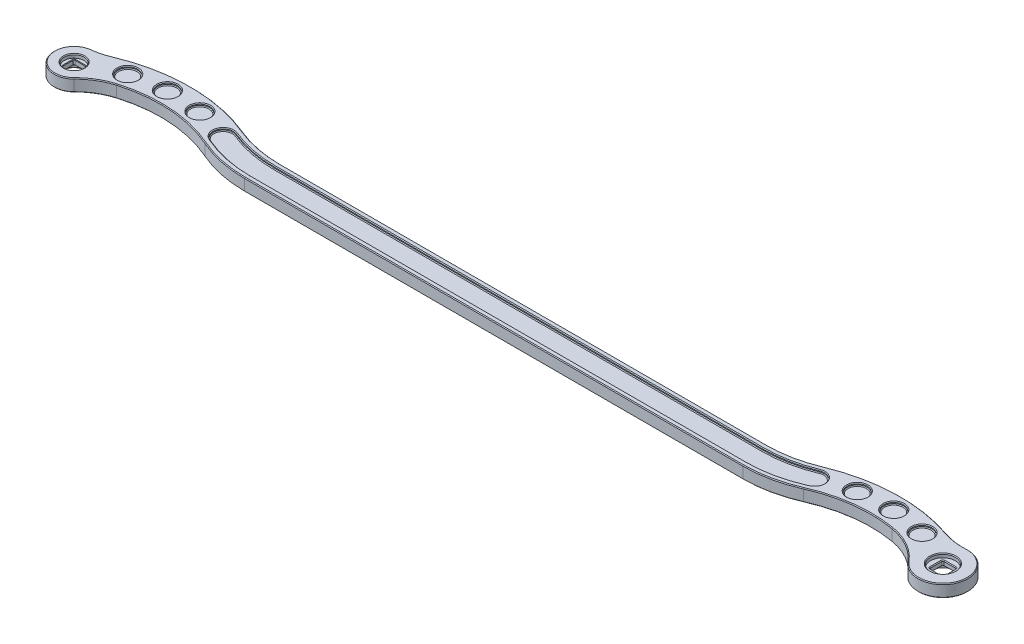
SolidWorks part; units mm, degrees
material "보통 탄소강"
ref_plane "정면" through (0, 0, 0) normal (0, 0, 1) x (1, 0, 0)
ref_plane "윗면" through (0, 0, 0) normal (0, 1, 0) x (1, 0, 0)
ref_plane "우측면" through (0, 0, 0) normal (1, 0, 0) x (0, 0, -1)
sketch "스케치1" plane through (0, 0, 0) normal (0, 1, 0) x (1, 0, 0)
  line L0 (0, 0) -> (350, 0) construction
  line L1 (77.0777, 6) -> (272.9223, 6)
  line L2 (74.6146, -6) -> (275.3854, -6)
  line L3 (335, 6.5992) -> (318, -52.3889) construction
  line L4 (75.0349, -4) -> (274.9651, -4)
  line L5 (0, 0) -> (32, 0) construction
  line L6 (32, 3) -> (32, 15) construction
  line L7 (32, 3) -> (32, 9) construction
  line L8 (175, 6) -> (175, -6) construction
  line L9 (273.3234, 4) -> (76.6766, 4)
  line L10 (307.4208, 8.0816) -> (318, -52.3889) construction
  line L11 (321.2949, 8.9115) -> (318, -52.3889) construction
  line L12 (294.089, 4.1521) -> (318, -52.3889) construction
  line L14 (347.25, -2.75) -> (352.75, -2.75)
  line L15 (347.25, -2.75) -> (347.25, 2.75)
  line L16 (347.25, 2.75) -> (352.75, 2.75)
  line L17 (352.75, -2.75) -> (352.75, 2.75)
  line L18 (347.25, -2.75) -> (352.75, 2.75) construction
  line L19 (347.25, 2.75) -> (352.75, -2.75) construction
  line L20 (2.5, -2.5) -> (-2.5, -2.5)
  line L21 (2.5, -2.5) -> (2.5, 2.5)
  line L22 (2.5, 2.5) -> (-2.5, 2.5)
  line L23 (-2.5, -2.5) -> (-2.5, 2.5)
  line L24 (2.5, -2.5) -> (-2.5, 2.5) construction
  line L25 (2.5, 2.5) -> (-2.5, -2.5) construction
  circle A2 centre (0, 0) radius 8
  circle A3 centre (350, 0) radius 10
  circle A6 centre (350, 0) radius 5
  circle A9 centre (32, 0) radius 3
  arc A11 (72.1368, -5.9386) -> (-6.5409, -4.6061) centre (32, -52.3889) ccw
  arc A12 (54.3968, -1.7301) -> (16.393, 0.7557) centre (32, -52.3889) ccw
  arc A13 (57.8775, 9.8334) -> (5.8839, 9.7336) centre (32, -52.3889) ccw
  arc A14 (57.3175, 7.8999) -> (13.8923, 10.4428) centre (32, -52.3889) ccw
  arc A15 (54.9979, 0.1904) -> (16.1077, 2.7556) centre (32, -52.3889) ccw
  circle A16 centre (15, 6.5992) radius 4
  circle A17 centre (32, -52.3889) radius 67.3889 construction
  circle A18 centre (32, -52.3889) radius 65.3889 construction
  circle A19 centre (32, -52.3889) radius 57.3889 construction
  circle A20 centre (32, -52.3889) radius 55.3889 construction
  arc A21 (64, 0) -> (18.8776, 7.5811) centre (32, -52.3889) ccw
  arc A22 (77.0777, 6) -> (57.8775, 9.8334) centre (77.0777, 56) cw
  arc A23 (76.6766, 4) -> (57.3175, 7.8999) centre (76.6766, 54) cw
  arc A24 (54.3968, -1.7301) -> (74.6146, -6) centre (74.6146, 44) ccw
  arc A25 (75.0349, -4) -> (54.9979, 0.1904) centre (75.0349, 46) cw
  arc A27 (295.0021, 0.1904) -> (333.8923, 2.7556) centre (318, -52.3889) cw
  arc A28 (274.9651, -4) -> (295.0021, 0.1904) centre (274.9651, 46) ccw
  arc A29 (295.6032, -1.7301) -> (275.3854, -6) centre (275.3854, 44) cw
  arc A30 (272.9223, 6) -> (292.1225, 9.8334) centre (272.9223, 56) ccw
  arc A31 (273.3234, 4) -> (292.6825, 7.8999) centre (273.3234, 54) ccw
  circle A32 centre (335, 6.5992) radius 4
  arc A33 (292.6825, 7.8999) -> (336.1077, 10.4428) centre (318, -52.3889) cw
  arc A34 (292.1225, 9.8334) -> (339.9749, 11.3164) centre (318, -52.3889) cw
  arc A35 (295.6032, -1.7301) -> (327.3652, 2.2025) centre (318, -52.3889) cw
  arc A36 (339.9749, 11.3164) -> (349.4649, 9.9857) centre (348.1272, 34.9499) ccw
  arc A37 (342.3252, -6.4107) -> (327.3652, 2.2025) centre (323.1382, -22.4375) ccw
  circle A38 centre (321.2949, 8.9115) radius 4
  circle A39 centre (307.4208, 8.0816) radius 4
  circle A40 centre (294.089, 4.1521) radius 4.0002
  circle A42 centre (15, 6.5992) radius 4
  circle A43 centre (28.7051, 8.9115) radius 4
  circle A44 centre (42.5792, 8.0816) radius 4
  circle A45 centre (55.911, 4.1521) radius 4.0002
  arc A46 (-0.9224, 7.9467) -> (5.8839, 9.7336) centre (-3.8047, 32.7799) ccw
  arc A47 (16.393, 0.7557) -> (5.6818, -5.6318) centre (23.4373, -23.2313) ccw
  circle A48 centre (0, 0) radius 4
  point P53 (175, 0)
  point P54 (175, 0)
  dimension "D3" = 5.5
  dimension "D4" = 16
  dimension "D5" = 20
  dimension "D8" = 4
  dimension "D11" = 10
  dimension "D12" = 50
  dimension "D14" = 6
  dimension "D9" = 2
  dimension "D18" = 50
  dimension "D19" = 13
  dimension "D21" = 13
  dimension "D22" = 8
  dimension "D23" = 50
  dimension "D24" = 25
  dimension "D27" = 8
  dimension "D1" = 350
  dimension "D6" = 6
  dimension "D7" = 6
  dimension "D10" = 4
  dimension "D13" = 32
  dimension "D15" = 12
  dimension "D17" = 15
  dimension "D20" = 13
  dimension "D26" = 5
  dimension "D16" = 2
extrude "보스-돌출1" add sketch "스케치1" along normal mid plane 2 contours A6 | A11 A48 L23 L22 L21 | A11 A48 L21 L20 L23 region at (-2.0344, 0, -3.3307) region at (-2.8693, 0, 1.9794) region at (345.1414, 0, 0)
extrude "보스-돌출3" add sketch "스케치1<4>" along normal mid plane 5 contours L4 A25 A11 A24 L2 A3 L1 A22 A13 A2 A16 A14 A23 A37 | A11 A2 | A2 A11 | A11 A25 A15 A16 A2 A12 A24 | A3 A6 | A6 | A11 A43 A14 A16 | A15 A43 A11 A16 | A11 A44 A14 A43 | A15 A44 A11 A43 | A11 A45 A14 A44 | A15 A45 A11 A44 | A40 A27 A39 A33 | A39 A27 A38 A33 | A38 A27 A32 A33 region at (175, 0, -5.649) region at (3.6453, 0, -6.8996) region at (356.6847, 0, -7.0525) region at (2.1307, 0, 3.4883) region at (9.3758, 0, -3.9532) region at (21.4174, 0, -10.3344) region at (22.1641, 0, -5.9089) region at (35.7983, 0, -11.1074) region at (35.5303, 0, -6.6274) region at (49.9842, 0, -8.6256) region at (48.7156, 0, -4.3206) region at (300.6197, 0, -6.5764) region at (314.3292, 0, -8.9749) region at (328.2271, 0, -8.2279) region at (345.1414, 0, 0)
sketch "스케치1<4>" plane through (0, 0, 0) normal (0, 1, 0) x (1, 0, 0) same geometry as "스케치1"
extrude "보스-돌출2" add sketch "스케치1<3>" along normal mid plane 3 contours L0 A37 | L0 L4 A37 | A37 L0 | L0 A37 | L0 | L0 | A25 A11 A16 A15 | A11 A16 | A16 A11 | A32 | A43 A21 | A43 A21 | A44 A21 | A44 A21 | A45 A21 | A45 A21 | A40 | A39 | A38 region at (175, 0, -5.649) region at (14.5364, 0, -8.2077) region at (15.4766, 0, -4.9456) region at (28.6153, 0, -10.5831) region at (28.7975, 0, -7.1931) region at (42.8677, 0, -9.7305) region at (42.2826, 0, -6.3864) region at (62.0542, 0, 0.7851) region at (55.2406, 0, -2.5669) region at (176.8355, 0, -0.1502) region at (56.563, 0, -5.6939) region at (294.089, 0, -4.1521) region at (307.4208, 0, -8.0816) region at (321.2949, 0, -8.9115) region at (335, 0, -6.5992)
sketch "스케치1<3>" plane through (0, 0, 0) normal (0, 1, 0) x (1, 0, 0) same geometry as "스케치1"
extrude "컷-돌출1" cut sketch "스케치1<6>" against normal blind 1.5 from surface contours A6 region at (345.1414, 0, 0) starting at face at (0, 2.5, 4)
sketch "스케치1<6>" plane through (0, 0, 0) normal (0, 1, 0) x (1, 0, 0) same geometry as "스케치1"
extrude "컷-돌출2" cut sketch "스케치1<7>" along normal blind 1.5 from surface contours A6 region at (345.1414, 0, 0) starting at face at (0, -2.5, 4)
sketch "스케치1<7>" plane through (0, 0, 0) normal (0, 1, 0) x (1, 0, 0) same geometry as "스케치1"
chamfer "모따기1" distance 0.3 angle 45 42 edges at (335, 1.5, -2.5992) (321.2949, 1.5, -4.9115) (307.4208, 1.5, -4.0816) (295.3241, 1.5, -0.3301) (285.2003, 1.5, 2.9412) (297.7775, 1.5, -5.7003) (283.1274, 1.5, -4.9706) (175, 1.5, -4) (175, 1.5, 4) (64.7997, 1.5, 2.9412) (66.8726, 1.5, -4.9706) (54.6759, 1.5, -0.3301) (52.2225, 1.5, -5.7003) (42.5792, 1.5, -4.0816) (28.7051, 1.5, -4.9115) (15, 1.5, -2.5992) (15, -1.5, -2.5992) (28.7051, -1.5, -4.9115) (42.5792, -1.5, -4.0816) (285.2003, -2.5, 2.9412) (295.3241, -2.5, -0.3301) (175, -2.5, 4) (297.7775, -2.5, -5.7003) (64.7997, -2.5, 2.9412) (283.1274, -2.5, -4.9706) (54.6759, -2.5, -0.3301) (175, -2.5, -4) (52.2225, -2.5, -5.7003) (66.8726, -2.5, -4.9706) (52.2225, -1.5, -5.7003) (66.8726, -1.5, -4.9706) (54.6759, -1.5, -0.3301) (64.7997, -1.5, 2.9412) (175, -1.5, 4) (175, -1.5, -4) (285.2003, -1.5, 2.9412) (295.3241, -1.5, -0.3301) (283.1274, -1.5, -4.9706) (297.7775, -1.5, -5.7003) (307.4208, -1.5, -4.0816) (321.2949, -1.5, -4.9115) (335, -1.5, -2.5992)
chamfer "모따기4" distance 0.3 angle 45 54 edges at (307.4208, 2.5, -4.0816) (335, 2.5, -2.5992) (321.2949, 2.5, -4.9115) (285.2003, 2.5, 2.9412) (295.3241, 2.5, -0.3301) (297.7775, 2.5, -5.7003) (283.1274, 2.5, -4.9706) (175, 2.5, 4) (175, 2.5, -4) (64.7997, 2.5, 2.9412) (54.6759, 2.5, -0.3301) (66.8726, 2.5, -4.9706) (52.2225, 2.5, -5.7003) (42.5792, 2.5, -4.0816) (28.7051, 2.5, -4.9115) (15, 2.5, -2.5992) (15, -2.5, -2.5992) (28.7051, -2.5, -4.9115) (42.5792, -2.5, -4.0816) (307.4208, -2.5, -4.0816) (321.2949, -2.5, -4.9115) (335, -2.5, -2.5992) (335.6122, -2.5, 0.7719) (311.194, -2.5, -2.5803) (285.7173, -2.5, 4.9209) (175, -2.5, 6) (64.2827, -2.5, 4.9209) (35.6153, -2.5, -2.8819) (-7.1942, -2.5, 3.499) (31.8707, -2.5, -14.9999) (67.2882, -2.5, -6.9677) (175, -2.5, -6) (282.7118, -2.5, -6.9677) (315.9126, -2.5, -14.9677) (344.6556, -2.5, -10.1921) (359.1685, -2.5, 3.9924) (359.1685, 2.5, 3.9924) (335.6122, 2.5, 0.7719) (344.6556, 2.5, -10.1921) (311.194, 2.5, -2.5803) (315.9126, 2.5, -14.9677) (285.7173, 2.5, 4.9209) (282.7118, 2.5, -6.9677) (175, 2.5, -6) (175, 2.5, 6) (64.2827, 2.5, 4.9209) (67.2882, 2.5, -6.9677) (35.6153, 2.5, -2.8819) (31.8707, 2.5, -14.9999) (-7.1942, 2.5, 3.499) (10.6327, -2.5, 1.7594) (2.5439, -2.5, -8.5995) (2.5439, 2.5, -8.5995) (10.6327, 2.5, 1.7594)
fillet "필렛1" radius 0.5 8 edges at (347.25, 0, -2.75) (347.25, 0, 2.75) (352.75, 0, 2.75) (352.75, 0, -2.75) (-2.5, 0, 2.5) (2.5, 0, 2.5) (2.5, 0, -2.5) (-2.5, 0, -2.5)
chamfer "모따기5" distance 0.3 angle 45 19 edges at (350, 2.5, 5) (350, -1, 2.75) (347.25, -1, 0) (352.75, -1, 0) (350, -1, -2.75) (350, 1, 2.75) (352.75, 1, 0) (347.25, 1, 0) (350, 1, -2.75) (0, 2.5, 4) (0, -2.5, 4) (347.3964, -1, 2.6036) (352.6036, -1, 2.6036) (347.3964, -1, -2.6036) (352.6036, -1, -2.6036) (352.6036, 1, 2.6036) (347.3964, 1, 2.6036) (352.6036, 1, -2.6036) (347.3964, 1, -2.6036)
chamfer "모따기6" distance 0.2 angle 45 16 edges at (0, -1, 2.5) (-2.5, -1, 0) (2.5, -1, 0) (0, -1, -2.5) (0, 1, 2.5) (2.5, 1, 0) (-2.5, 1, 0) (0, 1, -2.5) (2.3536, -1, 2.3536) (-2.3536, -1, 2.3536) (2.3536, -1, -2.3536) (-2.3536, -1, -2.3536) (2.3536, 1, 2.3536) (-2.3536, 1, 2.3536) (2.3536, 1, -2.3536) (-2.3536, 1, -2.3536)
